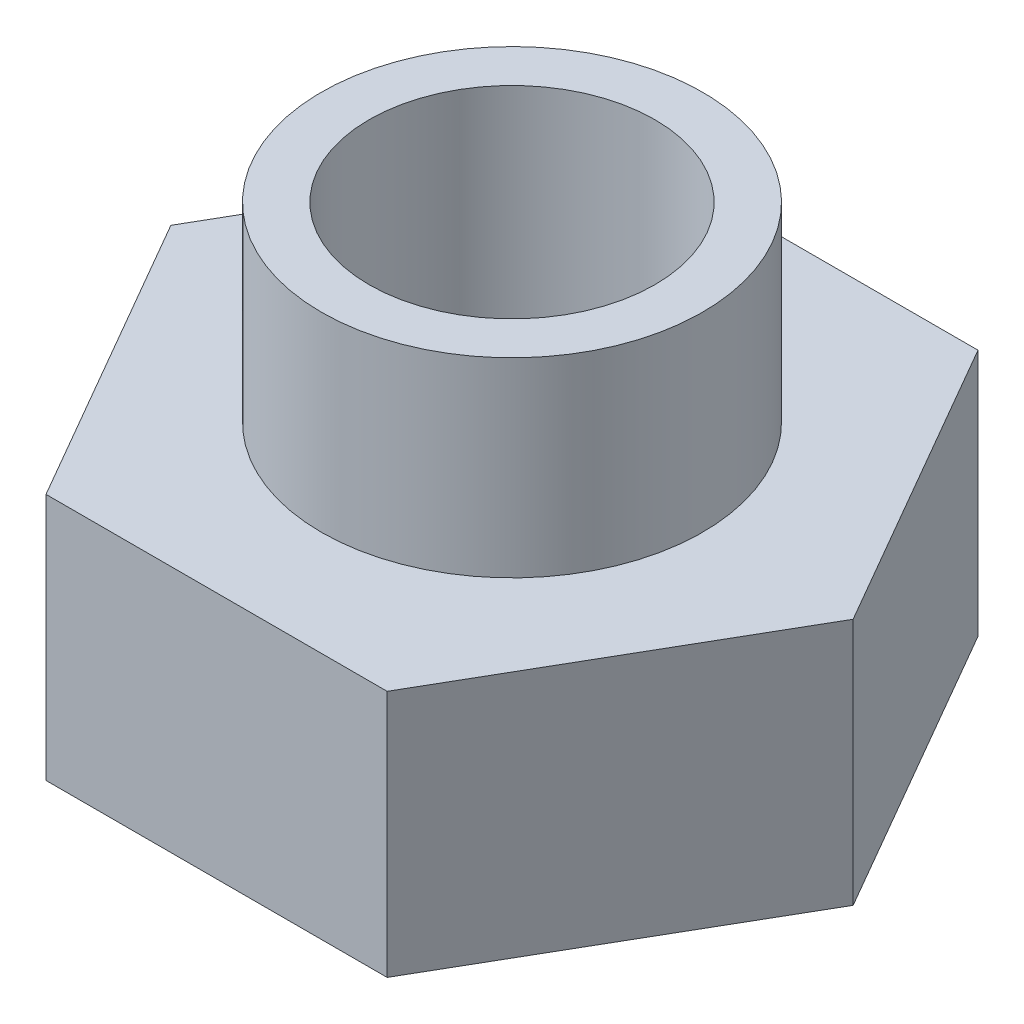
SolidWorks part; units mm, degrees
ref_plane "Front Plane" through (0, 0, 0) normal (0, 0, 1) x (1, 0, 0)
ref_plane "Top Plane" through (0, 0, 0) normal (0, 1, 0) x (1, 0, 0)
ref_plane "Right Plane" through (0, 0, 0) normal (1, 0, 0) x (0, 0, -1)
sketch "Sketch1" plane through (0, 0, 0) normal (0, 1, 0) x (1, 0, 0)
  line L1 (44.7446, -77.5) -> (89.4893, 0)
  line L2 (89.4893, 0) -> (44.7446, 77.5)
  line L3 (44.7446, 77.5) -> (-44.7446, 77.5)
  line L4 (-44.7446, 77.5) -> (-89.4893, 0)
  line L5 (-89.4893, 0) -> (-44.7446, -77.5)
  line L6 (-44.7446, -77.5) -> (44.7446, -77.5)
  circle A0 centre (0, 0) radius 77.5 construction
  circle A1 centre (0, 0) radius 50
  circle A2 centre (0, 0) radius 37.5
  dimension "D2" = 75
  dimension "D3" = 100
  dimension "D1" = 155
extrude "Boss-Extrude1" add sketch "Sketch1" along normal blind 65 contours L5 L6 L1 L2 L3 L4 A1 region at (0, 0, 75.1323)
extrude "Boss-Extrude2" add sketch "Sketch1<3>" along normal blind 115 contours A1 A2 region at (-48.5858, 0, 0)
sketch "Sketch1<3>" plane through (0, 0, 0) normal (0, 1, 0) x (1, 0, 0) same geometry as "Sketch1"
